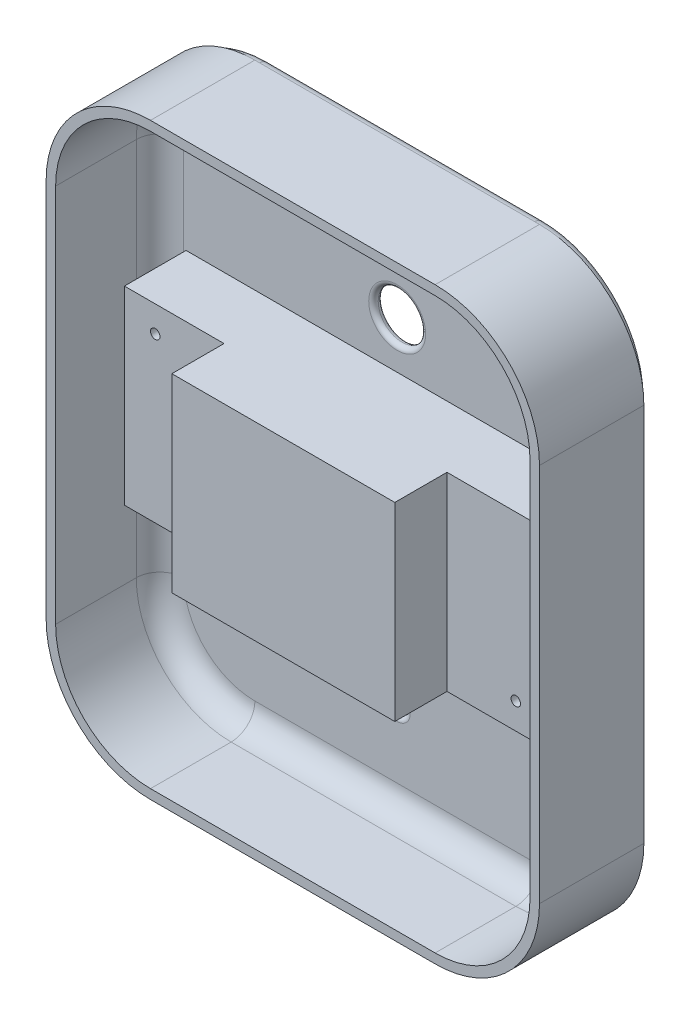
SolidWorks part; units mm, degrees
ref_plane "Front Plane" through (0, 0, 0) normal (0, 0, 1) x (1, 0, 0)
ref_plane "Top Plane" through (0, 0, 0) normal (0, 1, 0) x (1, 0, 0)
ref_plane "Right Plane" through (0, 0, 0) normal (1, 0, 0) x (0, 0, -1)
sketch "Sketch1" plane through (0, 0, 0) normal (0, 0, 1) x (1, 0, 0)
  line L0 (0, 60) -> (0, -60) construction
  line L5 (-30, 60) -> (30, 60)
  line L6 (-50, 40) -> (-50, -40)
  line L7 (-30, -60) -> (30, -60)
  line L8 (50, 40) -> (50, -40)
  line L9 (-50, 0) -> (50, 0) construction
  line L10 (-30, 62) -> (30, 62)
  line L11 (52, 40) -> (52, -40)
  line L12 (-30, -62) -> (30, -62)
  line L13 (-52, 40) -> (-52, -40)
  arc A2 (50, 40) -> (30, 60) centre (30, 40) ccw
  arc A3 (50, -40) -> (30, -60) centre (30, -40) cw
  arc A4 (-30, -60) -> (-50, -40) centre (-30, -40) cw
  arc A5 (-50, 40) -> (-30, 60) centre (-30, 40) cw
  arc A6 (52, 40) -> (30, 62) centre (30, 40) ccw
  arc A7 (52, -40) -> (30, -62) centre (30, -40) cw
  arc A8 (-30, -62) -> (-52, -40) centre (-30, -40) cw
  arc A9 (-52, 40) -> (-30, 62) centre (-30, 40) cw
  point P17 (50, 60)
  point P23 (-50, -60)
  point P26 (-50, 60)
  dimension "D5" = 20
  dimension "D3" = 100
  dimension "D4" = 120
  dimension "D6" = 2
extrude "Boss-Extrude1" add sketch "Sketch1" along normal blind 22
sketch "Sketch3" plane through (0, 0, 0) normal (0, 0, 1) x (1, 0, 0)
  line L0 (-23.5, -20) -> (-23.5, 20)
  line L1 (-23.5, -20) -> (23.5, -20)
  line L2 (23.5, -20) -> (23.5, 20)
  line L3 (-23.5, 20) -> (23.5, 20)
  line L4 (-23.5, 0) -> (23.5, 0) construction
  line L5 (0, 20) -> (0, -20) construction
  line L7 (38, -16.75) -> (38, 0) construction
  line L9 (38, -16.75) -> (0, -16.75) construction
  point P13 (0, 0)
  point P17 (0, 0)
  dimension "D1" = 47
  dimension "D2" = 40
extrude "Boss-Extrude2" add sketch "Sketch3" along normal blind 24
sketch "Sketch7" plane through (0, 0, 0) normal (0, 0, -1) x (-1, 0, 0)
  line L0 (-23.5, -20) -> (-23.5, 20) construction
  line L1 (-44.5, -20) -> (44.5, -20)
  line L2 (-44.5, -20) -> (-44.5, 20)
  line L3 (-44.5, 20) -> (44.5, 20)
  line L4 (44.5, -20) -> (44.5, 20)
  line L5 (-38, -14.5) -> (0, -14.5) construction
  line L6 (38, 14.5) -> (0, 14.5) construction
  line L7 (-38, -14.5) -> (-38, 0) construction
  line L8 (38, 14.5) -> (38, 0) construction
  circle A2 centre (-38, -14.5) radius 1
  circle A3 centre (38, 14.5) radius 1
  point P4 (0, -20)
  point P6 (-44.5, 0)
  point P13 (0, 0)
  point P18 (0, 0)
  point P19 (0, 0)
  dimension "D4" = 2
  dimension "D1" = 89
  dimension "D2" = 76
  dimension "D3" = 29
extrude "Boss-Extrude4" add sketch "Sketch7" against normal blind 13 separate body
sketch "Sketch6" plane through (0, 0, 0) normal (0, 0, 1) x (1, 0, 0)
  line L0 (-29, 62) -> (29, 62)
  line L1 (51, 40) -> (51, -40)
  line L2 (-29, -62) -> (29, -62)
  line L3 (-51, 40) -> (-51, -40)
  line L6 (0, 0) -> (7.7555, 0) construction
  arc A0 (51, 40) -> (29, 62) centre (29, 40) ccw
  arc A1 (51, -40) -> (29, -62) centre (29, -40) cw
  arc A2 (-29, -62) -> (-51, -40) centre (-29, -40) cw
  arc A3 (-51, 40) -> (-29, 62) centre (-29, 40) cw
  circle A4 centre (0, 41) radius 1.75
  circle A5 centre (0, -41) radius 1.75
  circle A6 centre (0, 30) radius 5
  circle A7 centre (0, -30) radius 5
  dimension "D2" = 3.5
  dimension "D3" = 10
  dimension "D1" = 82
  dimension "D4" = 30
extrude "Boss-Extrude3" add sketch "Sketch6" against normal blind 2 separate body
sketch "Sketch4" plane through (0, 0, 0) normal (0, 0, 1) x (1, 0, 0)
  line L1 (-37.5, 55) -> (37.5, 55)
  line L2 (-37.5, 55) -> (-37.5, -55)
  line L3 (-37.5, -55) -> (37.5, -55)
  line L4 (37.5, 55) -> (37.5, -55)
  line L5 (-28.5, 50) -> (28.5, 50)
  line L6 (-28.5, 50) -> (-28.5, -50)
  line L7 (-28.5, -50) -> (28.5, -50)
  line L8 (28.5, 50) -> (28.5, -50)
  point P4 (-37.5, 0)
  point P6 (0, 55)
  point P11 (0, 50)
  point P12 (-28.5, 0)
  dimension "D1" = 75
  dimension "D2" = 110
  dimension "D3" = 57
  dimension "D4" = 100
combine bodies "Combine1" operation type add bodies to combine 101 103
fillet "Fillet10" radius 5 8 edges at (50, 0, 0) (44.1421, -54.1421, 0) (0, -60, 0) (-44.1421, -54.1421, 0) (-50, 0, 0) (-44.1421, 54.1421, 0) (0, 60, 0) (44.1421, 54.1421, 0)
fillet "Fillet12" radius 2 8 edges at (-44.5563, -55.5563, -2) (0, -62, -2) (44.5563, -55.5563, -2) (51, 0, -2) (44.5563, 55.5563, -2) (0, 62, -2) (-51, 0, -2) (-44.5563, 55.5563, -2)
fillet "Fillet13" radius 1 2 edges at (5, 30, -2) (5, 30, 0)
fillet "Fillet14" radius 1 6 edges at (5, -30, 0) (1.75, 41, 0) (1.75, 41, -2) (1.75, -41, -2) (1.75, -41, 0) (5, -30, -2)
combine bodies "Combine2" operation type add bodies to combine 107 102
